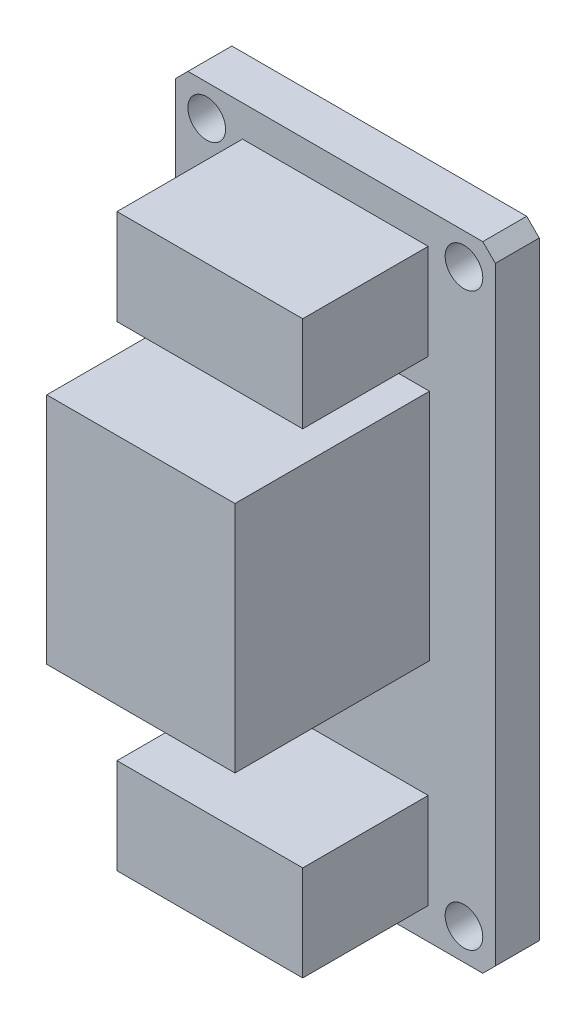
SolidWorks part; units mm, degrees
ref_plane "Front Plane" through (0, 0, 0) normal (0, 0, 1) x (1, 0, 0)
ref_plane "Top Plane" through (0, 0, 0) normal (0, 1, 0) x (1, 0, 0)
ref_plane "Right Plane" through (0, 0, 0) normal (1, 0, 0) x (0, 0, -1)
sketch "Sketch1" plane through (0, 0, 0) normal (0, 0, 1) x (1, 0, 0)
  line L1 (0, 0) -> (25.5, 0)
  line L2 (0, 0) -> (0, 50.5)
  line L3 (0, 50.5) -> (25.5, 50.5)
  line L4 (25.5, 0) -> (25.5, 50.5)
  line L6 (20.15, 48) -> (5.35, 48)
  line L7 (5.35, 48) -> (5.35, 40.4)
  line L8 (5.35, 40.4) -> (20.15, 40.4)
  line L9 (20.15, 40.4) -> (20.15, 48)
  line L10 (20.25, 38.0486) -> (5.25, 38.0486)
  line L11 (5.25, 38.0486) -> (5.25, 19.4486)
  line L12 (5.25, 19.4486) -> (20.25, 19.4486)
  line L13 (20.25, 19.4486) -> (20.25, 38.0486)
  line L14 (20.15, 10.1) -> (20.15, 2.5)
  line L15 (5.35, 10.1) -> (20.15, 10.1)
  line L16 (5.35, 2.5) -> (5.35, 10.1)
  line L17 (20.15, 2.5) -> (5.35, 2.5)
  circle A0 centre (2.5, 48) radius 1.5
  circle A1 centre (2.5, 2.5) radius 1.5
  circle A2 centre (23, 2.5) radius 1.5
  circle A3 centre (23, 48) radius 1.5
  point P20 (12.75, 48)
  point P25 (12.75, 38.0486)
  dimension "D3" = 2.5
  dimension "D4" = 2.5
  dimension "D5" = 2.5
  dimension "D10" = 45.5
  dimension "D11" = 20.5
  dimension "D1" = 25.5
  dimension "D2" = 50.5
  dimension "D6" = 14.8
  dimension "D7" = 7.6
  dimension "D8" = 15
  dimension "D9" = 18.6
extrude "Boss-Extrude1" add sketch "Sketch1" against normal blind 3.5 contours L1 L4 L3 L2 A1 A0 L13 L12 L11 L10 L9 L8 L7 L6 L14 L17 L16 L15 A2 A3 | L8 L9 L6 L7 | L12 L13 L10 L11 | L17 L14 L15 L16 region at (0.5657, 25.25, 0) region at (12.75, 44.2, 0) region at (12.75, 28.7486, 0) region at (12.75, 6.3, 0)
extrude "Boss-Extrude2" add sketch "Sketch1<4>" along normal blind 10 contours L8 L9 L6 L7 | L17 L14 L15 L16 region at (12.75, 44.2, 0) region at (12.75, 6.3, 0)
sketch "Sketch1<4>" plane through (0, 0, 0) normal (0, 0, 1) x (1, 0, 0) same geometry as "Sketch1"
extrude "Boss-Extrude3" add sketch "Sketch1<6>" along normal blind 15.5 contours L12 L13 L10 L11 region at (12.75, 28.7486, 0)
sketch "Sketch1<6>" plane through (0, 0, 0) normal (0, 0, 1) x (1, 0, 0) same geometry as "Sketch1"
chamfer "Chamfer1" distance 1 angle 45 4 edges at (25.5, 0, -1.75) (0, 0, -1.75) (25.5, 50.5, -1.75) (0, 50.5, -1.75)
